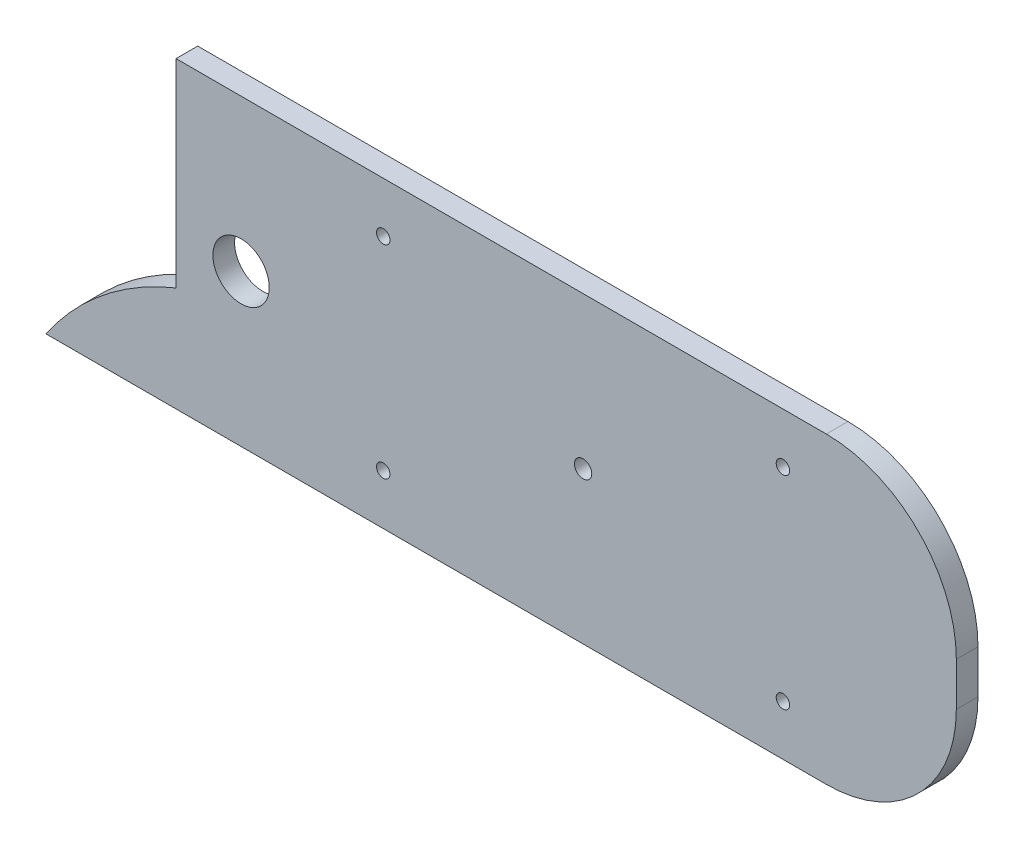
SolidWorks part; units mm, degrees
material "1060 Alloy"
ref_plane "Front Plane" through (0, 0, 0) normal (0, 0, 1) x (1, 0, 0)
ref_plane "Top Plane" through (0, 0, 0) normal (0, 1, 0) x (1, 0, 0)
ref_plane "Right Plane" through (0, 0, 0) normal (1, 0, 0) x (0, 0, -1)
sketch "Sketch2" plane through (0, 0, 0) normal (0, 0, 1) x (1, 0, 0)
  line L0 (0, 0) -> (457.2, 0)
  line L1 (76.2, 0) -> (76.2, 142.4009) construction
  line L2 (152.4, 0) -> (152.4, 186.487) construction
  line L9 (457.2, 177.8) -> (152.4, 177.8)
  line L14 (533.4, 76.2) -> (533.4, 101.6)
  line L15 (152.4, 177.8) -> (76.2, 177.8)
  line L16 (76.2, 177.8) -> (76.2, 61.4013)
  arc A5 (0, 0) -> (76.2, 61.4013) centre (138.3869, -93.7571) cw
  arc A6 (457.2, 0) -> (533.4, 76.2) centre (457.2, 76.2) ccw
  arc A7 (533.4, 101.6) -> (457.2, 177.8) centre (457.2, 101.6) ccw
  dimension "D6" = 167.1566
  dimension "D7" = 142.4009
  dimension "D5" = 177.8
  dimension "D1" = 76.2
  dimension "D4" = 457.2
  dimension "D9" = 138.3869
  dimension "D2" = 76.2
  dimension "D3" = 152.4
  dimension "D8" = 186.487
extrude "Boss-Extrude1" add sketch "Sketch2" along normal blind 12.7
sketch "Sketch4" plane through (0, 0, 12.7) normal (0, 0, 1) x (1, 0, 0)
  line L0 (314.706, 0) -> (314.706, 177.8) construction
  line L1 (0, 0) -> (457.2, 0) construction
  line L2 (457.2, 177.8) -> (76.2, 177.8) construction
  line L3 (76.2, 88.9) -> (533.4, 88.9) construction
  line L4 (76.2, 177.8) -> (76.2, 61.4013) construction
  line L6 (533.4, 76.2) -> (533.4, 101.6) construction
  circle A0 centre (314.706, 88.9) radius 5.08
  circle A3 centre (431.8, 148.336) radius 3.937
  circle A5 centre (197.612, 148.336) radius 3.937
  circle A6 centre (197.612, 29.464) radius 3.937
  circle A7 centre (431.8, 29.464) radius 3.937
  dimension "D1" = 10.16
  dimension "D4" = 7.874
  dimension "D5" = 29.464
  dimension "D6" = 117.094
  dimension "D2" = 314.706
  dimension "D3" = 88.9
extrude "Cut-Extrude2" cut sketch "Sketch4" against normal through all
sketch "Sketch5" plane through (0, 0, 12.7) normal (0, 0, 1) x (1, 0, 0)
  line L0 (114.3, 0) -> (114.3, 88.9) construction
  line L1 (0, 0) -> (457.2, 0) construction
  line L3 (76.2, 177.8) -> (76.2, 61.4013) construction
  circle A0 centre (114.3, 88.9) radius 16.51
  dimension "D3" = 33.02
  dimension "D1" = 88.9
  dimension "D2" = 38.1
extrude "Cut-Extrude3" cut sketch "Sketch5" against normal through all
equation "\"0.5n\"=0.25"
equation "\".5n\"=0.25"
